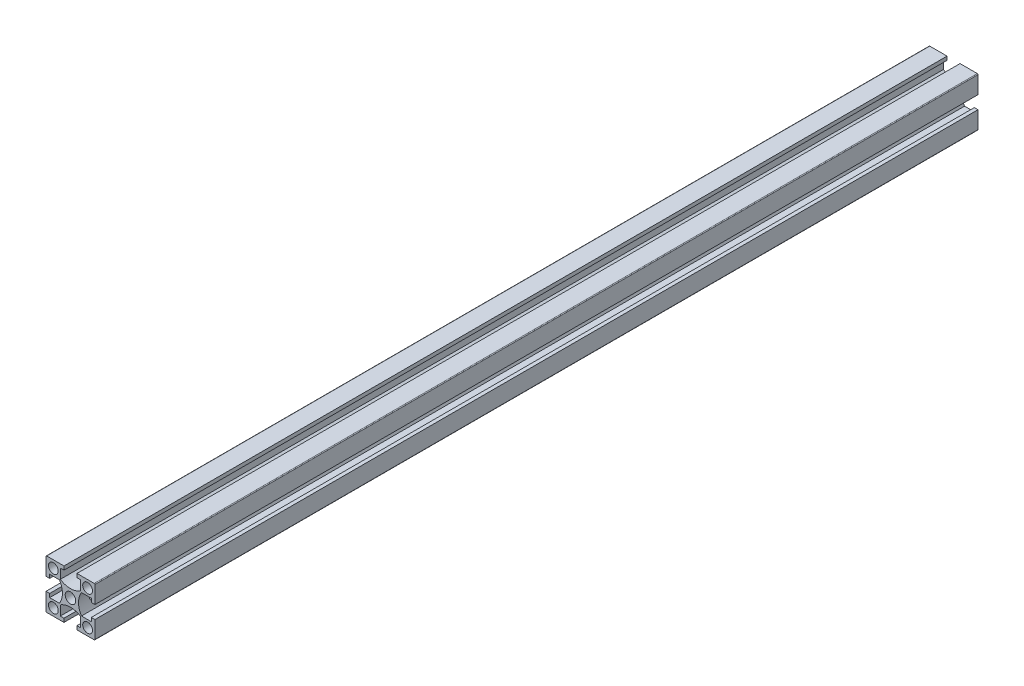
SolidWorks part; units mm, degrees
material "3.0255 (EN-AW 1350A)"
ref_plane "정면" through (0, 0, 0) normal (0, 0, 1) x (1, 0, 0)
ref_plane "윗면" through (0, 0, 0) normal (0, 1, 0) x (1, 0, 0)
ref_plane "우측면" through (0, 0, 0) normal (1, 0, 0) x (0, 0, -1)
sketch "스케치1" plane through (0, 0, 0) normal (0, 0, 1) x (1, 0, 0)
  line L0 (0, 32.0265) -> (0, -31.6588) construction
  line L1 (-10, 10) -> (-10, -10)
  line L2 (-10, 10) -> (10, 10)
  line L3 (-10, 2.65) -> (-8.5, 2.65)
  line L4 (13.6618, 0) -> (-11.6993, 0) construction
  line L5 (-8.5, 2.65) -> (-8.5, 4.15)
  line L6 (-8.5, 4.15) -> (-4.5032, 4.15)
  line L7 (-10, -2.65) -> (-8.5, -2.65)
  line L8 (-8.5, -2.65) -> (-8.5, -4.15)
  line L9 (-8.5, -4.15) -> (-4.5032, -4.15)
  line L10 (-10, -10) -> (10, -10)
  line L11 (10, 10) -> (10, -10)
  circle A0 centre (-7, 7) radius 2
  circle A1 centre (-7, -7) radius 2
  arc A2 (-4.5032, 4.15) -> (-4.5032, -4.15) centre (-11.0587, 0) cw
  circle A3 centre (0, 0) radius 2.15
  circle A4 centre (7, 7) radius 2
  circle A5 centre (7, -7) radius 2
  point P21 (-10, 0)
  point P23 (-3.3, 0)
  point P31 (0, -10)
  point P32 (0, 10)
  dimension "D3" = 4
  dimension "D9" = 6.7
  dimension "D10" = 4.3
  dimension "D11" = 7.7587
  dimension "D1" = 20
  dimension "D2" = 20
  dimension "D4" = 14
  dimension "D5" = 14
  dimension "D6" = 5.3
  dimension "D7" = 8.3
  dimension "D8" = 1.5
extrude "보스-돌출1" add sketch "스케치1" along normal blind 361 contours A0 | A4 | A3 | A5 | A1 | A2 L6 L5 L3 L1 L7 L8 L9 | L2 L11 L10 L1 region at (-6.6069, 0, 0) region at (-7, 7, 0) region at (-7, -7, 0) region at (0, 0, 0) region at (7, 7, 0) region at (7, -7, 0)
extrude "컷-돌출1" cut sketch "스케치1<3>" along normal up to next contours A2 L6 L5 L3 L1 L7 L8 L9 region at (-6.6069, 0, 0)
sketch "스케치1<3>" plane through (0, 0, 0) normal (0, 0, 1) x (1, 0, 0) same geometry as "스케치1"
pattern_circular "원형 패턴1" count 4 over 360 about axis through (0, 0, 361) along (0, 0, -1) of "컷-돌출1" reverse direction yes
fillet "필렛1" radius 0.3 4 edges at (10, -10, 180.5) (-10, -10, 180.5) (-10, 10, 180.5) (10, 10, 180.5)
sketch "스케치4" plane through (0, 10, 0) normal (0, 1, 0) x (1, 0, 0)
  line L0 (-4.15, -361) -> (4.15, -361) construction
  line L1 (2.65, 0) -> (9.7, 0) construction
  circle A1 centre (0, -56) radius 2.15
  circle A2 centre (0, -108) radius 2.15
  circle A4 centre (0, -351) radius 2.15
  circle A5 centre (0, -271) radius 2.15
  dimension "D1" = 10
  dimension "D2" = 52
  dimension "D3" = 108
  dimension "D4" = 80
extrude "컷-돌출3" cut sketch "스케치4" against normal through all
sketch "스케치6" plane through (-10, 0, 0) normal (-1, 0, 0) x (0, 0, 1)
  line L0 (281, -73) -> (361, 7) construction
  line L1 (361, 10) -> (281, 10)
  line L2 (361, 10) -> (361, 7)
  line L3 (361, 7) -> (281, 7)
  line L4 (281, 10) -> (281, 7)
  line L5 (361, 7) -> (281, 7)
  line L6 (361, 7) -> (361, -73)
  line L7 (361, -73) -> (281, -73)
  line L8 (281, 7) -> (281, -73)
  circle A0 centre (321, -33) radius 47
  circle A1 centre (287.766, -66.234) radius 2.5
  circle A2 centre (287.766, 0.234) radius 2.5
  circle A3 centre (354.234, 0.234) radius 2.5
  circle A4 centre (354.234, -66.234) radius 2.5
  point P20 (321, -33)
  dimension "D4" = 4
  dimension "D5" = 5
  dimension "D1" = 3
  dimension "D2" = 80
  dimension "D3" = 80
extrude "컷-돌출4" cut sketch "스케치6" against normal through all contours A2 | A3
